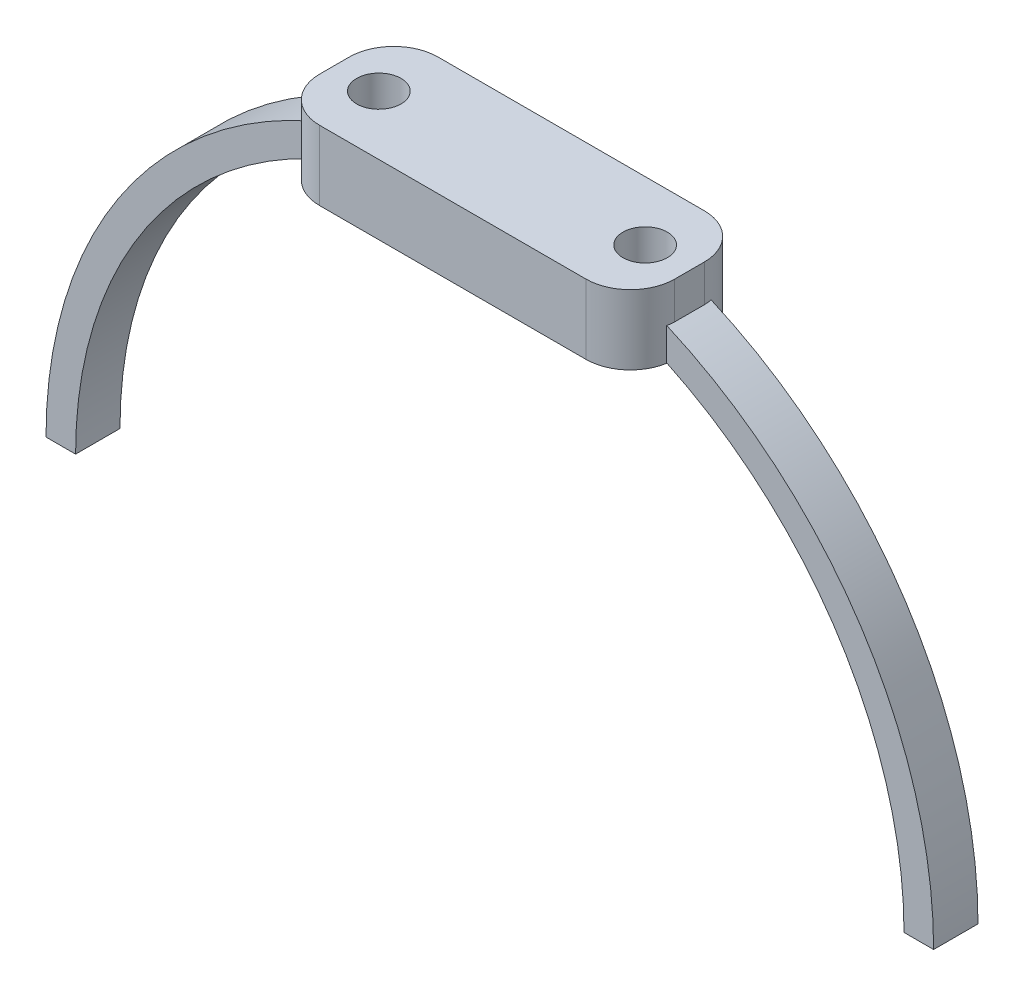
SolidWorks part; units mm, degrees
ref_plane "前视基准面" through (0, 0, 0) normal (0, 0, 1) x (1, 0, 0)
ref_plane "上视基准面" through (0, 0, 0) normal (0, 1, 0) x (1, 0, 0)
ref_plane "右视基准面" through (0, 0, 0) normal (1, 0, 0) x (0, 0, -1)
sketch "草图2" plane through (0, 0, 0) normal (0, 1, 0) x (1, 0, 0)
  line L1 (12, 4) -> (-12, 4)
  line L2 (12, 4) -> (12, -4)
  line L3 (12, -4) -> (-12, -4)
  line L4 (-12, 4) -> (-12, -4)
  line L5 (12, 4) -> (-12, -4) construction
  line L6 (12, -4) -> (-12, 4) construction
  point P0 (0, 0)
extrude "凸台-拉伸1" add sketch "草图2" against normal blind 1
sketch "草图5" plane through (0, 0, 0) normal (0, 0, 1) x (1, 0, 0)
  line L0 (0, 0) -> (0, -30) construction
  line L1 (-30, -30) -> (-28, -30)
  line L2 (30, -30) -> (28, -30)
  arc A0 (0, 0) -> (-30, -30) centre (0, -30) ccw
  arc A1 (0, 0) -> (30, -30) centre (0, -30) cw
  arc A2 (28, -30) -> (-28, -30) centre (0, -30) ccw
  dimension "D1" = 30
  dimension "D2" = 2
extrude "凸台-拉伸3" add sketch "草图5" along normal blind 1.5 and the other way blind 1.5 separate body contours A1 L0 A2 L2 | L0 A0 L1 A2 | L1 A0 A1 L2 A2 region at (20.9132, -9.0868, 0) region at (-0.4243, -1, 0)
sketch "草图7" plane through (0, 0, 4) normal (0, 0, 1) x (1, 0, 0)
  line L0 (-12, 0) -> (12, 0) construction
  line L1 (-12, 0) -> (12, 0) construction
  line L3 (-12, 0) -> (12, 0)
  line L4 (-12, 0) -> (-12, -4.7018)
  line L5 (-12, -4.7018) -> (12, -4.7018)
  line L6 (12, 0) -> (12, -4.7018)
  arc A0 (28, -30) -> (-28, -30) centre (0, -30) ccw construction
  arc A1 (28, -30) -> (-28, -30) centre (0, -30) ccw construction
extrude "凸台-拉伸5" add sketch "草图7" against normal up to surface (8 mm away) up to face at (0, -0.5, -4)
sketch "草图3" plane through (0, 0, 0) normal (0, 1, 0) x (1, 0, 0)
  circle A0 centre (0, 0) radius 9 construction
  circle A1 centre (-9, 0) radius 1.5
  circle A2 centre (9, 0) radius 1.5
extrude "切除-拉伸1" cut sketch "草图3" against normal through all
fillet "圆角1" radius 3 4 edges at (-12, -2.3509, 4) (-12, -2.3509, -4) (12, -2.3509, 4) (12, -2.3509, -4)
